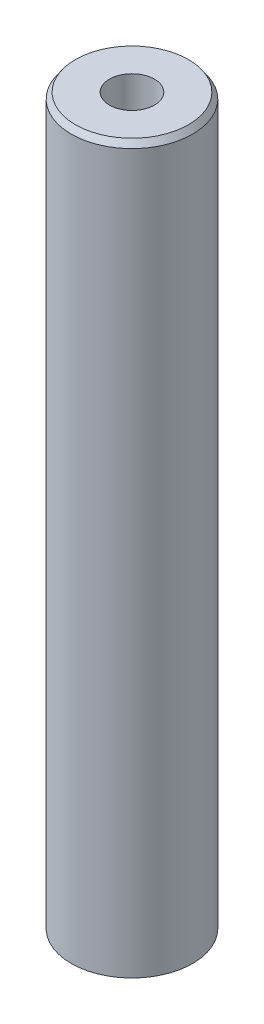
SolidWorks part; units mm, degrees
ref_plane "Front Plane" through (0, 0, 0) normal (0, 0, 1) x (1, 0, 0)
ref_plane "Top Plane" through (0, 0, 0) normal (0, 1, 0) x (1, 0, 0)
ref_plane "Right Plane" through (0, 0, 0) normal (1, 0, 0) x (0, 0, -1)
sketch "Sketch1" plane through (0, 0, 0) normal (0, 1, 0) x (1, 0, 0)
  circle A0 centre (0, 0) radius 50
  dimension "SHAFT_OD" = 100
extrude "Boss-Extrude1" add sketch "Sketch1" along normal blind 600
sketch "Sketch2" plane through (0, 0, 0) normal (0, 1, 0) x (1, 0, 0)
  circle A0 centre (0, 0) radius 18.5527
  dimension "BORE_D" = 37.1054
extrude "Cut-Extrude1" cut sketch "Sketch2" along normal through all
chamfer "Chamfer1" distance 4.9612 angle 34.964 2 edges at (0, 600, 50) (0, 0, 50) first distance on face at (0, 600, 50) first distance on face at (0, 0, 18.5527)
